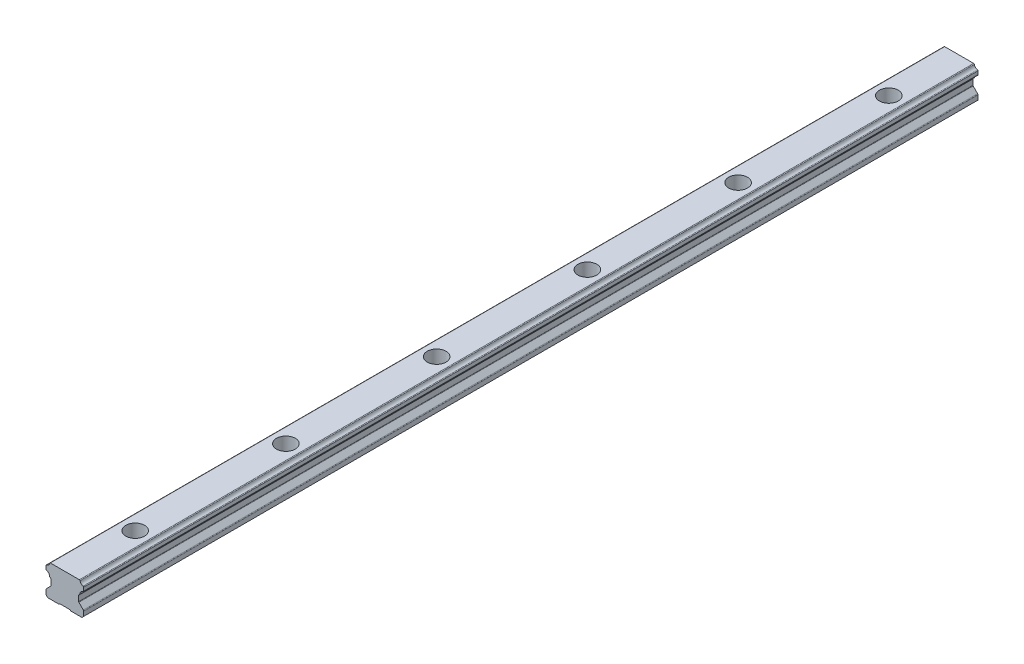
SolidWorks part; units mm, degrees
note: '?' marks a value the reader was unsure of.
ref_plane "Front Plane" through (0, 0, 0) normal (0, 0, 1) x (1, 0, 0)
ref_plane "Top Plane" through (0, 0, 0) normal (0, 1, 0) x (1, 0, 0)
ref_plane "Right Plane" through (0, 0, 0) normal (1, 0, 0) x (0, 0, -1)
ref_axis "Axis_X" through (-8.25, 0, 0) along (1, 0, 0)?
ref_axis "Axis_Y" through (0, 13.125, 0) along (0, -1, 0)?
ref_axis "Axis_Z" through (0, 0, -345.8) along (0, 0, 1)?
ref_plane "Plane1" through (0, 0, 28) normal (0, 0, 1) x (1, 0, 0)
sketch "Sketch1" plane through (0, 0, 28) normal (0, 0, 1) x (1, 0, 0)
  line L0 (-2.05, 0.3) -> (0, 0.3)
  line L1 (0, 0) -> (0, 12.5) construction
  line L2 (-2.05, 0.3) -> (-2.35, 0)
  line L3 (-2.35, 0) -> (-7.5, 0)
  line L5 (-7.5, 0) -> (-7.5, 2.7)
  line L6 (-7.5, 2.7) -> (-5.5, 4.7)
  line L7 (-5.5, 4.7) -> (-5.5, 7.1)
  line L8 (-5.5, 7.1) -> (-7.5, 7.1)
  line L9 (0, 12.5) -> (0, 0.3)
  line L14 (-7.5, 12.5) -> (-7.5, 7.1)
  line L29 (-7.5, 12.5) -> (0, 12.5)
  dimension "KSS_1" = 0.3
  dimension "MSM_3" = 2.7
  dimension "FIX_1" = 45
  dimension "MSM_4" = 7.1
  dimension "MSM_2" = 4.1
  dimension "WR" = 15
  dimension "HR" = 12.5
  dimension "MSM_1" = 11
extrude "Boss-Extrude101" add sketch "Sketch1" against normal blind 356
sketch "Sketch2" plane through (0, 0, 28) normal (0, 0, 1) x (1, 0, 0)
  line L0 (0, 0) -> (0, 12.5) construction
  line L1 (-7.5, 0) -> (-2.35, 0) construction
  line L2 (-5.5, 7.1) -> (-6.0305, 7.6305)
  line L3 (-5.5, 4.7) -> (-7.5, 2.7) construction
  line L4 (-5.5, 7.1) -> (-5.5, 4.7)
  line L5 (-5.5, 4.7) -> (-7.5, 2.7)
  line L6 (-7.5, 2.7) -> (-7.53, 6.17)
  circle A0 centre (-7.53, 12.53) radius 1.5
  arc A1 (-6.0305, 7.6305) -> (-7.53, 6.17) centre (-7.53, 7.67) ccw
  dimension "MSM_5" = 3
  dimension "MSM_6" = 15.06
  dimension "MSM_7" = 4.86
  dimension "MSM_8" = 7.67
extrude "Cut-Extrude101" cut sketch "Sketch2" against normal through all
chamfer "Chamfer101" distance 0.7 1 edges at (-7.5, 0, -150)
fillet "Fillet101" radius 0.5 1 edges at (-7.5, 2.7, -150)
fillet "Fillet102" radius 0.3 1 edges at (-5.5, 7.1, -150)
fillet "Fillet103" radius 0.3 3 edges at (-7.5, 9.1697, -150) (-7.5, 11.0303, -150) (-6.0303, 12.5, -150)
fillet "Fillet104" radius 0.3 1 edges at (-5.5, 4.7, -150)
mirror "Mirror101" about plane through (0, 0, 0) normal (1, 0, 0) of "Fillet104", "Fillet103", "Fillet102", "Fillet101", "Chamfer101", "Cut-Extrude101", "Boss-Extrude101"
hole_wizard "CBORE101" positions "Sketch4" profile "Sketch3" counterbore size "M5" standard "JIS" end condition through all
sketch "Sketch4" plane through (0, 12.5, 0) normal (0, 1, 0) x (1, 0, 0)
  point P0 (0, 0)
sketch "Sketch3" plane through (0, 12.5, 0) normal (1, 0, 0) x (0, 0, 1)
  line L0 (0, 0) -> (0, 12.5)
  line L1 (0, 12.5) -> (2.25, 12.5)
  line L3 (2.25, 12.5) -> (2.25, 5.3)
  line L4 (2.25, 5.3) -> (3.75, 5.3)
  line L5 (3.75, 5.3) -> (3.75, 0)
  line L7 (3.75, 0) -> (0, 0)
  line L11 (0, -6.35) -> (0, 107.95) construction
  dimension "D_s" = 4.5
  dimension "Thru Hole Depth" = 12.5
  dimension "D" = 7.5
  dimension "H_s" = 5.3
pattern_linear "LPattern101" count 6 spacing 60 along (0, 0, -1) of "CBORE101"
hole_wizard "CBORE102" [suppressed] positions "Sketch6" profile "Sketch5" counterbore size "M5" standard "JIS"
sketch "Sketch6" [suppressed] plane through (0, 12.5, 0) normal (0, 1, 0) x (1, 0, 0)
  line L0 (5.7605, -20) -> (-5.7605, -20) construction
  point P0 (0, -19)
  dimension "ES" = 2
sketch "Sketch5" [suppressed] plane through (0, 12.5, 19) normal (1, 0, 0) x (0, 0, 1)
  line L0 (0, 0) -> (0, 12.5)
  line L1 (0, 12.5) -> (2.25, 12.5)
  line L3 (2.25, 12.5) -> (2.25, 5.3)
  line L4 (2.25, 5.3) -> (3.75, 5.3)
  line L5 (3.75, 5.3) -> (3.75, 0)
  line L7 (3.75, 0) -> (0, 0)
  line L11 (0, -6.35) -> (0, 107.95) construction
  dimension "D_s" = 4.5
  dimension "Thru Hole Depth" = 12.5
  dimension "D" = 7.5
  dimension "H_s" = 5.3
pattern_linear "LPattern102" [suppressed]
hole_wizard "CBORE103" [suppressed] positions "Sketch8" profile "Sketch7" counterbore size "M5" standard "JIS"
sketch "Sketch8" [suppressed] plane through (0, 12.5, 0) normal (0, 1, 0) x (1, 0, 0)
  line L0 (5.7605, 80) -> (-5.7605, 80) construction
  point P0 (0, 79)
  dimension "EB" = 2
sketch "Sketch7" [suppressed] plane through (0, 12.5, -79) normal (1, 0, 0) x (0, 0, 1)
  line L0 (0, 0) -> (0, 12.5)
  line L1 (0, 12.5) -> (2.25, 12.5)
  line L3 (2.25, 12.5) -> (2.25, 5.3)
  line L4 (2.25, 5.3) -> (3.75, 5.3)
  line L5 (3.75, 5.3) -> (3.75, 0)
  line L7 (3.75, 0) -> (0, 0)
  line L11 (0, -6.35) -> (0, 107.95) construction
  dimension "D_s" = 4.5
  dimension "Thru Hole Depth" = 12.5
  dimension "D" = 7.5
  dimension "H_s" = 5.3
pattern_linear "LPattern103" [suppressed]
equation "\"Factor\"= 1.082532"
equation "\"L\"=356"
equation "\"M_2\"=6"
equation "\"P\"=60"
equation "\"E@Plane1\" = ( \"L\" - ( ( \"M_2\" - 1 ) * \"P\" ) ) / 2"
equation "\"KSS_1@Sketch1\"= if ( \"WR@Sketch1\" = 15 , 0.3 , 0.5 )"
equation "\"KSS_2@Fillet101\"= if ( \"WR@Sketch1\" = 15 , 0.5 , 1.5 )"
equation "\"ES\"= 2"
equation "\"EB\"= 2"
equation "\"ES@Sketch6\"= iif ( \"ES\" > 2 * \"E@Plane1\" , 2 * \"E@Plane1\" , \"ES\" )"
equation "\"EB@Sketch8\"= iif ( \"EB\" > 2 * \"E@Plane1\" , 2 * \"E@Plane1\" , \"EB\" )"
